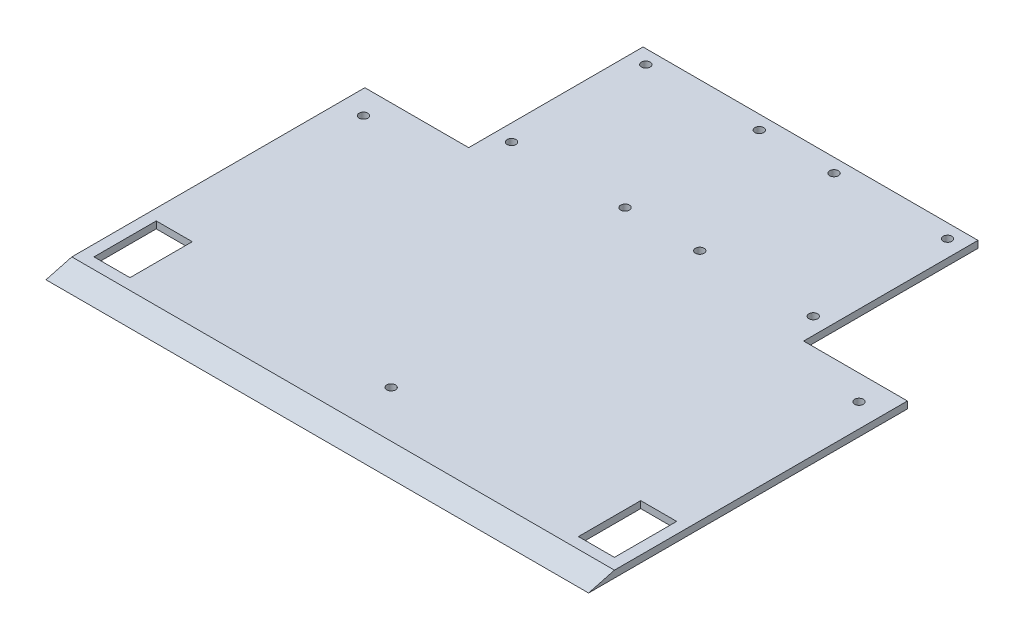
SolidWorks part; units mm, degrees
ref_plane "Alzado" through (0, 0, 0) normal (0, 0, 1) x (1, 0, 0)
ref_plane "Planta" through (0, 0, 0) normal (0, 1, 0) x (1, 0, 0)
ref_plane "Vista lateral" through (0, 0, 0) normal (1, 0, 0) x (0, 0, -1)
sketch "Croquis1" plane through (0, 0, 0) normal (1, 0, 0) x (0, 0, -1)
  line L0 (0, 0) -> (178.17, 0)
  line L1 (178.17, 0) -> (178.17, 2.5)
  line L2 (178.17, 2.5) -> (9.3301, 2.5)
  line L3 (0, 0) -> (9.3301, 2.5)
  dimension "D1" = 178.17
  dimension "D2" = 2.5
  dimension "D3" = 165
extrude "Saliente-Extruir1" add sketch "Croquis1" along normal blind 196
sketch "Croquis2" plane through (0, 0, 0) normal (0, -1, 0) x (-1, 0, 0)
  line L1 (-37.5, 115.1801) -> (0, 115.1801)
  line L2 (-37.5, 115.1801) -> (-37.5, 178.17)
  line L3 (-37.5, 178.17) -> (0, 178.17)
  line L4 (0, 115.1801) -> (0, 178.17)
  line L5 (-37.5, 115.1801) -> (0, 178.17) construction
  line L6 (-37.5, 178.17) -> (0, 115.1801) construction
  line L7 (-158.5, 115.1801) -> (-196, 115.1801)
  line L8 (-158.5, 115.1801) -> (-158.5, 178.17)
  line L9 (-158.5, 178.17) -> (-196, 178.17)
  line L10 (-196, 115.1801) -> (-196, 178.17)
  line L11 (-158.5, 115.1801) -> (-196, 178.17) construction
  line L12 (-158.5, 178.17) -> (-196, 115.1801) construction
  point P4 (-18.75, 146.6751)
  point P11 (-177.25, 146.6751)
extrude "Cortar-Extruir1" cut sketch "Croquis2" against normal up to next
sketch "Croquis4" plane through (0, 2.5, 0) normal (0, 1, 0) x (1, 0, 0)
  line L7 (4, 13.3301) -> (17, 13.3301)
  line L8 (4, 13.3301) -> (4, 35.8301)
  line L9 (4, 35.8301) -> (17, 35.8301)
  line L10 (17, 13.3301) -> (17, 35.8301)
  line L11 (4, 13.3301) -> (17, 35.8301) construction
  line L12 (4, 35.8301) -> (17, 13.3301) construction
  point P9 (10.5, 24.5801)
  dimension "D3" = 22.5
  dimension "D4" = 13
extrude "Cortar-Extruir2" cut sketch "Croquis4" against normal up to next
ref_plane "Plano1" through (98, 0, 0) normal (1, 0, 0) x (0, 0, -1)
mirror "Simetría1" about plane through (98, 0, 0) normal (1, 0, 0) of "Cortar-Extruir2"
sketch "Sketch1" plane through (0, 2.5, 0) normal (0, 1, 0) x (1, 0, 0)
  circle A0 centre (187.5, 106.1801) radius 1.585
  circle A1 centre (8.5, 106.1801) radius 1.585
extrude "Cut-Extrude1" cut sketch "Sketch1" against normal up to next
sketch "Sketch2" plane through (0, 2.5, 0) normal (0, 1, 0) x (1, 0, 0)
  circle A0 centre (98.5, 26.1801) radius 1.585
extrude "Cut-Extrude2" cut sketch "Sketch2" against normal up to next
sketch "Sketch3" plane through (0, 2.5, 0) normal (0, 1, 0) x (1, 0, 0)
  circle A0 centre (111.5, 124.67) radius 1.585
  circle A1 centre (152.5, 124.67) radius 1.585
  circle A2 centre (152.5, 173.17) radius 1.585
  circle A3 centre (111.5, 173.17) radius 1.585
  circle A4 centre (84.5, 173.17) radius 1.585
  circle A5 centre (43.5, 173.17) radius 1.585
  circle A6 centre (43.5, 124.67) radius 1.585
  circle A7 centre (84.5, 124.67) radius 1.585
extrude "Cut-Extrude3" cut sketch "Sketch3" against normal up to next
